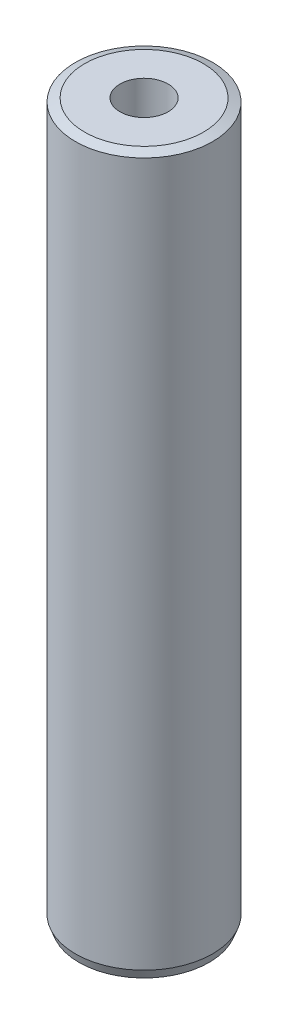
SolidWorks part; units mm, degrees
ref_plane "Front Plane" through (0, 0, 0) normal (0, 0, 1) x (1, 0, 0)
ref_plane "Top Plane" through (0, 0, 0) normal (0, 1, 0) x (1, 0, 0)
ref_plane "Right Plane" through (0, 0, 0) normal (1, 0, 0) x (0, 0, -1)
sketch "Sketch1" plane through (0, 0, 0) normal (0, 1, 0) x (1, 0, 0)
  circle A0 centre (0, 0) radius 57.5
  dimension "SHAFT_OD" = 115
extrude "Boss-Extrude1" add sketch "Sketch1" along normal blind 600
sketch "Sketch2" plane through (0, 0, 0) normal (0, 1, 0) x (1, 0, 0)
  circle A0 centre (0, 0) radius 20.1871
  dimension "BORE_D" = 40.3743
extrude "Cut-Extrude1" cut sketch "Sketch2" along normal through all
chamfer "Chamfer1" distance 2.9632 angle 69.066 2 edges at (0, 600, 57.5) (0, 0, 57.5) first distance on face at (0, 600, 57.5) first distance on face at (0, 0, 20.1871)
